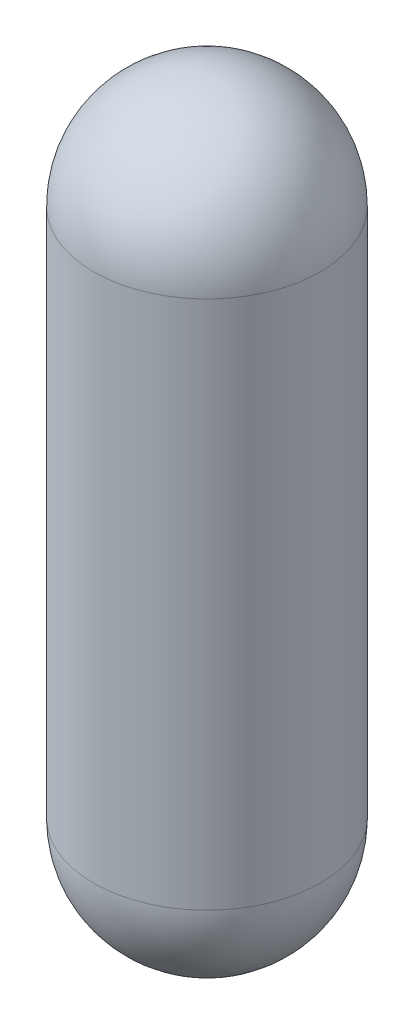
SolidWorks part; units mm, degrees
ref_plane "Front Plane" through (0, 0, 0) normal (0, 0, 1) x (1, 0, 0)
ref_plane "Top Plane" through (0, 0, 0) normal (0, 1, 0) x (1, 0, 0)
ref_plane "Right Plane" through (0, 0, 0) normal (1, 0, 0) x (0, 0, -1)
sketch "3DP Bed" plane through (0, 0, 0) normal (0, 0, 1) x (1, 0, 0)
  line L1 (0, 0) -> (225, 0) construction
  line L2 (0, 0) -> (0, 225) construction
  line L3 (0, 225) -> (225, 225) construction
  line L4 (225, 0) -> (225, 225) construction
  point P0 (110.1968, 110.1968)
  dimension "D1" = 225
ref_plane "Middle Top Plane" through (0, 110.1968, 0) normal (0, 1, 0) x (1, 0, 0)
ref_plane "Middle Right Plane" through (110.1968, 0, 0) normal (1, 0, 0) x (0, 0, -1)
sketch "Sketch1" plane through (0, 110.1968, 0) normal (0, 1, 0) x (1, 0, 0)
  circle A0 centre (110.1968, -15) radius 15
  point P0 (110.1968, 0)
  point P4 (91.4778, -28.3113)
  point P5 (0, 0)
  dimension "D1" = 30
extrude "Boss-Extrude1" add sketch "Sketch1" along normal blind 70
sketch "Sketch2" plane through (110.1968, 0, 0) normal (1, 0, 0) x (0, 0, -1)
  line L0 (-30, 110.1968) -> (0, 110.1968) construction
  line L1 (-30, 110.1968) -> (0, 110.1968)
  line L2 (0, 180.1968) -> (-30, 180.1968) construction
  line L3 (0, 180.1968) -> (-30, 180.1968)
  circle A0 centre (-15, 180.1968) radius 15
  circle A1 centre (-15, 110.1968) radius 15
revolve "Revolve1" add sketch "Sketch2" angle 360 about L3 region at (110.1968, 186.563, 15)
revolve "Revolve2" add sketch "Sketch2<3>" angle 360 about L1 region at (110.1968, 103.8306, 15)
sketch "Sketch2<3>" plane through (110.1968, 0, 0) normal (1, 0, 0) x (0, 0, -1) same geometry as "Sketch2"
